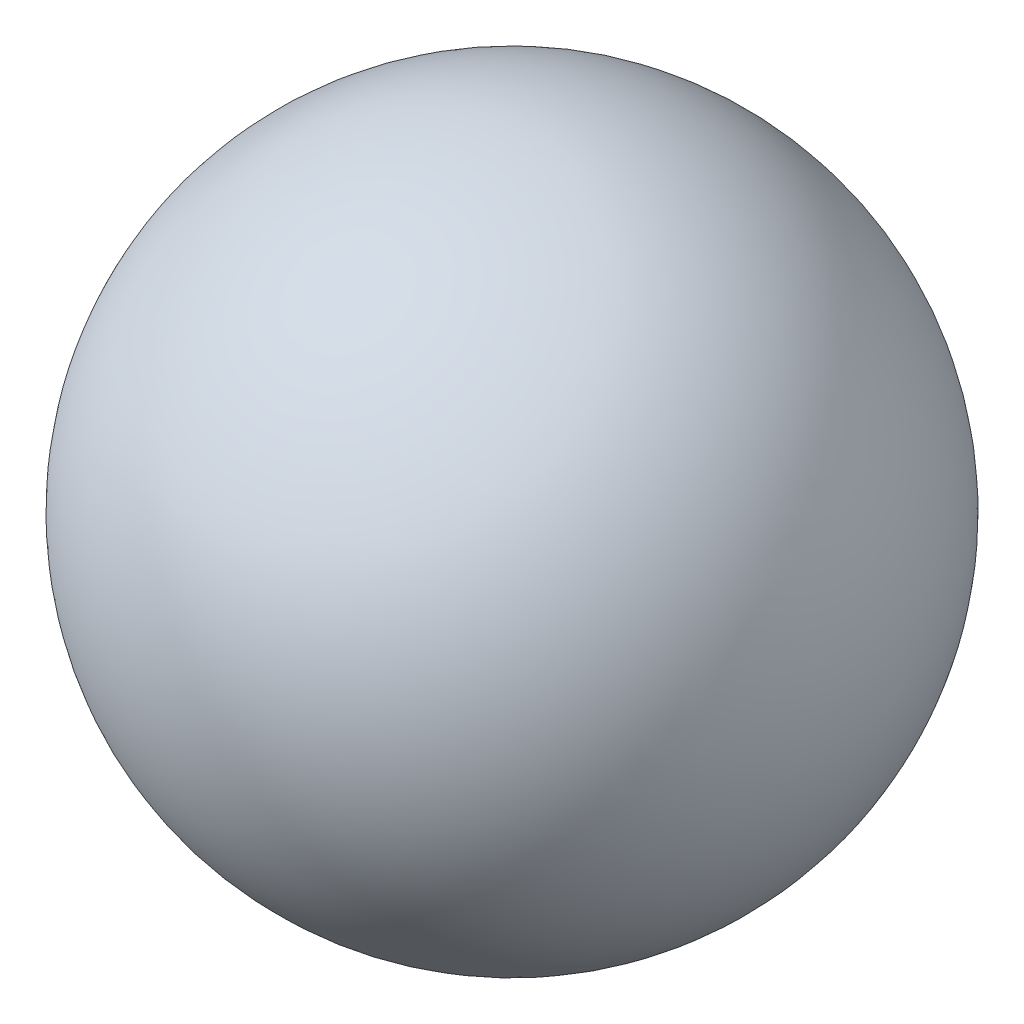
SolidWorks part; units mm, degrees
ref_plane "Front Plane" through (0, 0, 0) normal (0, 0, 1) x (1, 0, 0)
ref_plane "Top Plane" through (0, 0, 0) normal (0, 1, 0) x (1, 0, 0)
ref_plane "Right Plane" through (0, 0, 0) normal (1, 0, 0) x (0, 0, -1)
sketch "Sketch1" plane through (0, 0, 0) normal (0, 1, 0) x (1, 0, 0)
  line L0 (-17.5, 0) -> (17.5, 0)
  arc A0 (-17.5, 0) -> (17.5, 0) centre (0, 0) ccw
  dimension "D1" = 35
revolve "Revolve3" add sketch "Sketch1" angle 360 about L0
sketch "Sketch2" plane through (0, 0, 0) normal (1, 0, 0) x (0, 0, -1)
  point P0 (-25.1, -14.3)
  dimension "D1" = 14.3
  dimension "D2" = 25.1
ref_axis "Axis2" through (0, -14.3, 25.1) along (1, 0, 0)
